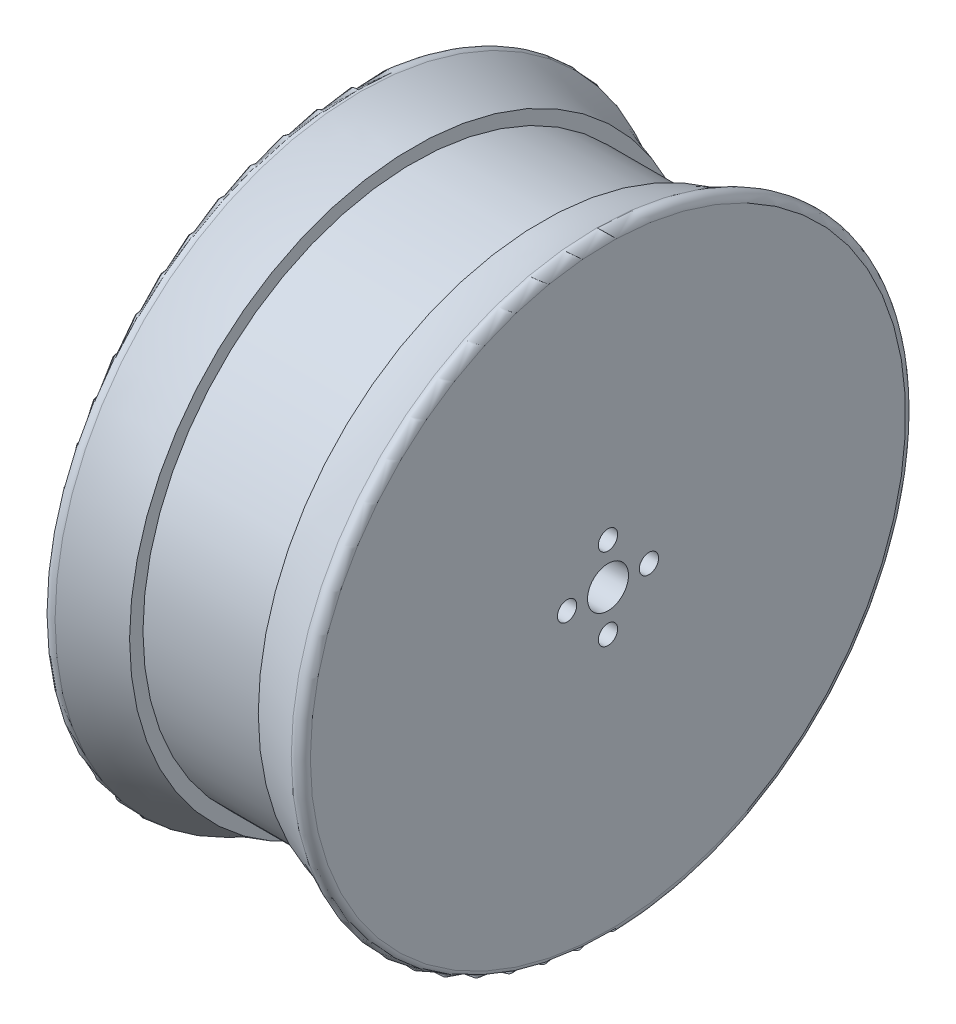
SolidWorks part; units mm, degrees
ref_plane "Front Plane" through (0, 0, 0) normal (0, 0, 1) x (1, 0, 0)
ref_plane "Top Plane" through (0, 0, 0) normal (0, 1, 0) x (1, 0, 0)
ref_plane "Right Plane" through (0, 0, 0) normal (1, 0, 0) x (0, 0, -1)
sketch "Wheel Arc" plane through (0, 0, 0) normal (0, 0, 1) x (1, 0, 0)
  line L0 (0, 0) -> (0, -103.7082) construction
  line L1 (-25.4, 0) -> (25.4, 0)
  line L2 (-40.9053, 0) -> (38.2322, 0) construction
  line L3 (-25.4, 0) -> (-25.4, -58.171)
  line L4 (25.4, 0) -> (25.4, -58.171)
  line L5 (0, -53.9082) -> (0, -52.9082) construction
  line L6 (-12.573, -52.9082) -> (12.573, -52.9082)
  line L7 (-12.573, -52.9082) -> (-12.573, -55.5215)
  line L8 (12.573, -52.9082) -> (12.573, -55.5215)
  arc A0 (23.0769, -59.5777) -> (12.573, -55.5215) centre (0, -103.7082) ccw
  arc A1 (-12.573, -55.5215) -> (-23.0769, -59.5777) centre (0, -103.7082) ccw
  arc A2 (25.4, -58.171) -> (23.0769, -59.5777) centre (23.8125, -58.171) cw
  arc A3 (-23.0769, -59.5777) -> (-25.4, -58.171) centre (-23.8125, -58.171) cw
  point P7 (0, 0)
  point P9 (0, 0)
  point P16 (0, -52.9082)
  dimension "D3" = 49.8
  dimension "D2" = 50.8
  dimension "D4" = 1
  dimension "D6" = 1.5875
  dimension "D1" = 103.7082
  dimension "D5" = 25.146
  dimension "D7" = 52.9082
ref_axis "Wheel Axis" through (-40.9053, 0, 0) along (1, 0, 0)
revolve "Wheel" add sketch "Wheel Arc" angle 360 about axis through (-40.9053, 0, 0) along (1, 0, 0)
sketch "Flower" plane through (25.4, 0, 0) normal (1, 0, 0) x (0, 0, -1)
  line L0 (0, 0) -> (0, 8) construction
  circle A0 centre (0, 0) radius 4
  circle A1 centre (0, 8) radius 1.885
  circle A2 centre (8, 0) radius 1.885
  circle A3 centre (0, -8) radius 1.885
  circle A4 centre (-8, 0) radius 1.885
  point P14 (0, 0)
  dimension "D1" = 4
extrude "Mounting" cut sketch "Flower" against normal through all
